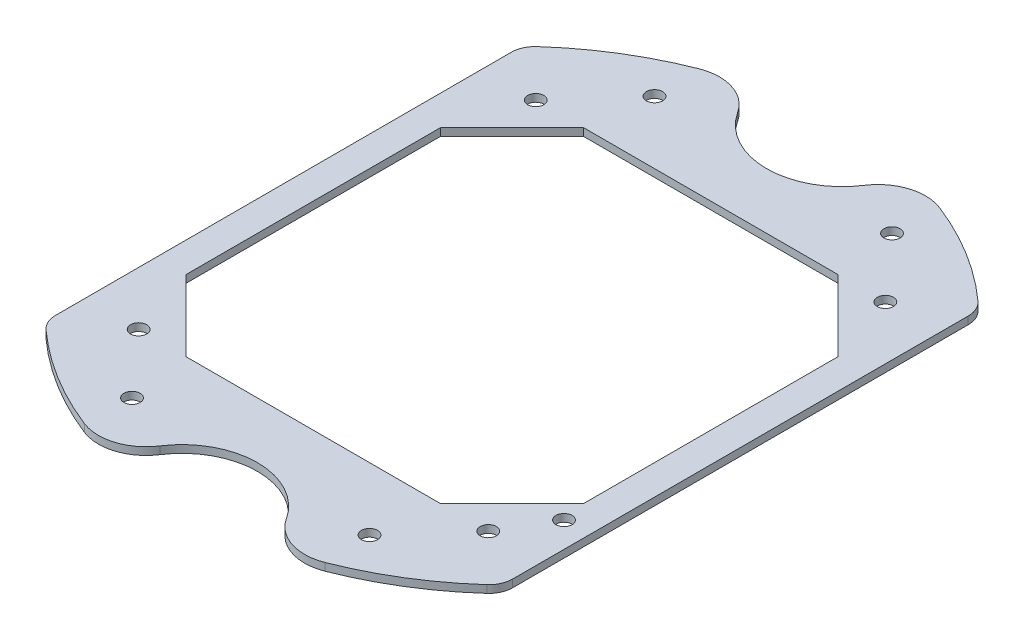
SolidWorks part; units mm, degrees
ref_plane "Front Plane" through (0, 0, 0) normal (0, 0, 1) x (1, 0, 0)
ref_plane "Top Plane" through (0, 0, 0) normal (0, 1, 0) x (1, 0, 0)
ref_plane "Right Plane" through (0, 0, 0) normal (1, 0, 0) x (0, 0, -1)
sketch "Sketch1" plane through (0, 0, 0) normal (0, 1, 0) x (1, 0, 0)
  line L1 (-46.8, -46.8) -> (46.8, -46.8) construction
  line L2 (-46.8, -46.8) -> (-46.8, 46.8)
  line L3 (-46.8, 46.8) -> (46.8, 46.8) construction
  line L4 (46.8, -46.8) -> (46.8, 46.8)
  line L5 (-46.8, -46.8) -> (46.8, 46.8) construction
  line L6 (-46.8, 46.8) -> (46.8, -46.8) construction
  line L8 (-48.0933, -47.9502) -> (-48.0933, 47.9502)
  line L10 (48.0933, -47.9502) -> (48.0933, 47.9502)
  arc A0 (-46.4355, -51.669) -> (-25.3447, -64.6807) centre (0, 0) ccw
  circle A1 centre (69.469, 0) radius 15.875 construction
  arc A2 (13.3113, -60.8189) -> (-13.3113, -60.8189) centre (0, -69.469) ccw
  arc A3 (-13.3113, 60.8189) -> (13.3113, 60.8189) centre (0, 69.469) ccw
  arc A4 (46.4355, 51.669) -> (25.3447, 64.6807) centre (0, 0) ccw
  arc A5 (25.3447, -64.6807) -> (46.4355, -51.669) centre (0, 0) ccw
  arc A6 (-25.3447, 64.6807) -> (-46.4355, 51.669) centre (0, 0) ccw
  arc A7 (13.3113, 60.8189) -> (25.3447, 64.6807) centre (21.6964, 55.3699) cw
  arc A8 (-13.3113, 60.8189) -> (-25.3447, 64.6807) centre (-21.6964, 55.3699) ccw
  arc A9 (13.3113, -60.8189) -> (25.3447, -64.6807) centre (21.6964, -55.3699) ccw
  arc A10 (-13.3113, -60.8189) -> (-25.3447, -64.6807) centre (-21.6964, -55.3699) cw
  arc A11 (-48.0933, 47.9502) -> (-46.4355, 51.669) centre (-43.0933, 47.9502) cw
  arc A12 (48.0933, 47.9502) -> (46.4355, 51.669) centre (43.0933, 47.9502) ccw
  arc A13 (48.0933, -47.9502) -> (46.4355, -51.669) centre (43.0933, -47.9502) cw
  arc A14 (-48.0933, -47.9502) -> (-46.4355, -51.669) centre (-43.0933, -47.9502) ccw
  circle A15 centre (-21.6964, 55.3699) radius 3.61 construction
  point P0 (0, 0)
  point P26 (-15.771, 67.6551)
  point P29 (15.771, -67.6551)
  point P34 (-48.0933, 50.1296)
  point P37 (48.0933, 50.1296)
  point P40 (48.0933, -50.1296)
  point P43 (-48.0933, -50.1296)
  dimension "D3" = 138.938
  dimension "D4" = 31.75
  dimension "D5" = 31.75
  dimension "D6" = 31.75
  dimension "D9" = 10
  dimension "D10" = 5
  dimension "D11" = 7.22
  dimension "D1" = 93.6
  dimension "D2" = 93.6
  dimension "D7" = 100.2592
  dimension "D8" = 100.2592
extrude "Boss-Extrude1" add sketch "Sketch1" against normal blind 1.6 contours A5 A13 L10 A12 A4 A7 A3 A8 A6 A11 L8 A14 A0 A10 A2 A9
hole_wizard "Enclosure Mounting Holes - M3 Clearance Hole1" positions "Sketch4" profile "Sketch5" hole size "M3" standard "ANSI Metric" end condition through all
sketch "Sketch4" plane through (0, 0, 0) normal (0, 1, 0) x (1, 0, 0)
  line L0 (-46.8, -46.8) -> (46.8, -46.8) construction
  line L1 (-46.8, -46.8) -> (-46.8, 46.8) construction
  line L2 (46.8, -46.8) -> (46.8, 46.8) construction
  line L3 (-46.8, 46.8) -> (46.8, 46.8) construction
  point P0 (-36.8, 41.8)
  point P2 (-36.8, -41.8)
  point P4 (36.8, -41.8)
  point P6 (36.8, 41.8)
  dimension "D1" = 5
  dimension "D2" = 10
  dimension "D3" = 10
  dimension "D4" = 5
  dimension "D5" = 10
  dimension "D6" = 5
  dimension "D7" = 5
  dimension "D8" = 10
sketch "Sketch5" plane through (-36.8, 0, -41.8) normal (1, 0, 0) x (0, 0, 1)
  line L0 (0, 0) -> (0, 1.6)
  line L1 (0, 1.6) -> (1.7, 1.6)
  line L2 (1.7, 1.6) -> (1.7, 0)
  line L5 (1.7, 0) -> (0, 0)
  line L11 (0, -6.35) -> (0, 107.95) construction
  dimension "Thru Hole Dia." = 3.4
  dimension "Thru Hole Depth" = 1.6
hole_wizard "Bulkhead Mounting Holes - M4x0.7 Tapped Hole1" positions "Sketch11" profile "Sketch10" hole size "M3" standard "ANSI Metric" end condition through all
sketch "Sketch11" plane through (0, 0, 0) normal (0, 1, 0) x (1, 0, 0)
  point P0 (-25, 55)
  point P3 (25, 55)
  point P6 (25, -55)
  point P9 (-25, -55)
  dimension "D1" = 55
  dimension "D2" = 25
  dimension "D3" = 25
  dimension "D4" = 55
  dimension "D5" = 55
  dimension "D6" = 25
  dimension "D7" = 25
  dimension "D8" = 55
sketch "Sketch10" plane through (-25, 0, -55) normal (1, 0, 0) x (0, 0, 1)
  line L0 (0, 0) -> (0, 1.6)
  line L1 (0, 1.6) -> (1.7, 1.6)
  line L2 (1.7, 1.6) -> (1.7, 0)
  line L5 (1.7, 0) -> (0, 0)
  line L11 (0, -6.35) -> (0, 107.95) construction
  dimension "Thru Hole Dia." = 3.4
  dimension "Thru Hole Depth" = 1.6
sketch "Sketch14" plane through (0, 0, 0) normal (0, 1, 0) x (1, 0, 0)
  line L0 (46.8, -46.8) -> (46.8, 46.8) construction
  line L1 (-46.8, -46.8) -> (46.8, -46.8) construction
  circle A0 centre (42.75, -31.8) radius 1.7
  dimension "D1" = 4.05
  dimension "D3" = 3.4
  dimension "D2" = 15
extrude "Cut-Extrude1" cut sketch "Sketch14" against normal through all contours A0
sketch "Sketch15" plane through (0, 0, 0) normal (0, 1, 0) x (1, 0, 0)
  line L0 (-1.1382, 6.3003) -> (-26.1448, 34.8691)
  line L8 (-5.8423, -0.9786) -> (-29.5197, -28.4852)
  line L9 (-32.1565, -27.5066) -> (-32.1565, 27.5066)
  line L10 (-32.1565, -37.3571) -> (32.1565, -37.3571)
  line L11 (-32.1565, -37.3571) -> (-32.1565, 37.3571)
  line L12 (-32.1565, 37.3571) -> (32.1565, 37.3571)
  line L13 (32.1565, -37.3571) -> (32.1565, 37.3571)
  line L14 (-32.1565, -37.3571) -> (32.1565, 37.3571) construction
  line L15 (-32.1565, 37.3571) -> (32.1565, -37.3571) construction
  line L16 (1.1274, 6.3097) -> (25.719, 34.8785)
  line L17 (24.5822, 37.3571) -> (-25.0161, 37.3571)
  line L18 (-32.1565, 0) -> (32.1565, 0) construction
  line L19 (24.5822, -37.3571) -> (-25.0161, -37.3571)
  line L20 (1.1274, -6.3097) -> (25.719, -34.8785)
  line L21 (-1.1382, -6.3003) -> (-26.1448, -34.8691)
  line L22 (-5.8423, 0.9786) -> (-29.5197, 28.4852)
  line L23 (0, 25) -> (0, -25) construction
  line L24 (32.1565, -27.5066) -> (32.1565, 27.5066)
  line L25 (5.8423, 0.9786) -> (29.5197, 28.4852)
  line L26 (5.8423, -0.9786) -> (29.5197, -28.4852)
  arc A0 (-26.1448, 34.8691) -> (-25.0161, 37.3571) centre (-25.0161, 35.8571) cw
  arc A1 (-1.1382, 6.3003) -> (1.1274, 6.3097) centre (-0.0095, 7.2883) ccw
  arc A2 (25.719, 34.8785) -> (24.5822, 37.3571) centre (24.5822, 35.8571) ccw
  arc A3 (32.1565, 27.5066) -> (29.5197, 28.4852) centre (30.6565, 27.5066) ccw
  arc A4 (32.1565, -27.5066) -> (29.5197, -28.4852) centre (30.6565, -27.5066) cw
  arc A5 (5.8423, 0.9786) -> (5.8423, -0.9786) centre (6.9792, 0) ccw
  arc A6 (1.1274, -6.3097) -> (-1.1382, -6.3003) centre (-0.0095, -7.2883) ccw
  arc A7 (24.5822, -37.3571) -> (25.719, -34.8785) centre (24.5822, -35.8571) ccw
  arc A8 (-25.0161, -37.3571) -> (-26.1448, -34.8691) centre (-25.0161, -35.8571) cw
  arc A9 (-5.8423, 0.9786) -> (-5.8423, -0.9786) centre (-6.9792, 0) cw
  arc A10 (-29.5197, -28.4852) -> (-32.1565, -27.5066) centre (-30.6565, -27.5066) cw
  arc A11 (-29.5197, 28.4852) -> (-32.1565, 27.5066) centre (-30.6565, 27.5066) ccw
  point P0 (0, 0)
  point P5 (0, 0)
  point P27 (-28.3226, 37.3571)
  point P30 (0, 5)
  point P33 (27.8526, 37.3571)
  point P36 (32.1565, 31.5485)
  point P39 (32.1565, -31.5485)
  point P42 (5, 0)
  point P45 (0, -5)
  point P48 (27.8526, -37.3571)
  point P51 (-28.3226, -37.3571)
  point P54 (-5, 0)
  point P57 (-32.1565, -31.5485)
  point P60 (-32.1565, 31.5485)
  dimension "D9" = 1.5
  dimension "D1" = 5
  dimension "D2" = 5
  dimension "D3" = 32.3571
  dimension "D4" = 81.917
  dimension "D5" = 42.6936
  dimension "D6" = 64.313
  dimension "D7" = 32.1565
  dimension "D8" = 5
extrude "Cut-Extrude2" [suppressed] cut sketch "Sketch15" against normal blind 10 contours L8 L22 L9 | L0 L16 L12 | L25 L26 L13 | L20 L21 L10
ref_plane "Plane1" through (0, 0, 0) normal (-1, 0, 0) x (0, 0, 1)
sketch "Sketch17" plane through (0, 0, 0) normal (0, 1, 0) x (1, 0, 0)
  line L0 (26.8, -41.8) -> (41.8, -26.8)
  line L1 (-26.8, -41.8) -> (26.8, -41.8)
  line L2 (-41.8, -26.8) -> (-41.8, 26.8)
  line L3 (-26.8, 41.8) -> (26.8, 41.8)
  line L4 (41.8, -26.8) -> (41.8, 26.8)
  line L5 (-41.8, -41.8) -> (41.8, 41.8) construction
  line L6 (-41.8, 41.8) -> (41.8, -41.8) construction
  line L7 (41.8, 26.8) -> (26.8, 41.8)
  line L8 (-41.8, 26.8) -> (-26.8, 41.8)
  line L9 (-26.8, -41.8) -> (-41.8, -26.8)
  point P0 (0, 0)
  dimension "D1" = 83.6
  dimension "D2" = 83.6
extrude "Cut-Extrude3" cut sketch "Sketch17" against normal blind 10 contours L9 L1 L0 L4 L7 L3 L8 L2 | L2 L8 L3 L7 L4 L0 L1 L9 region at (0, 0, 0)
